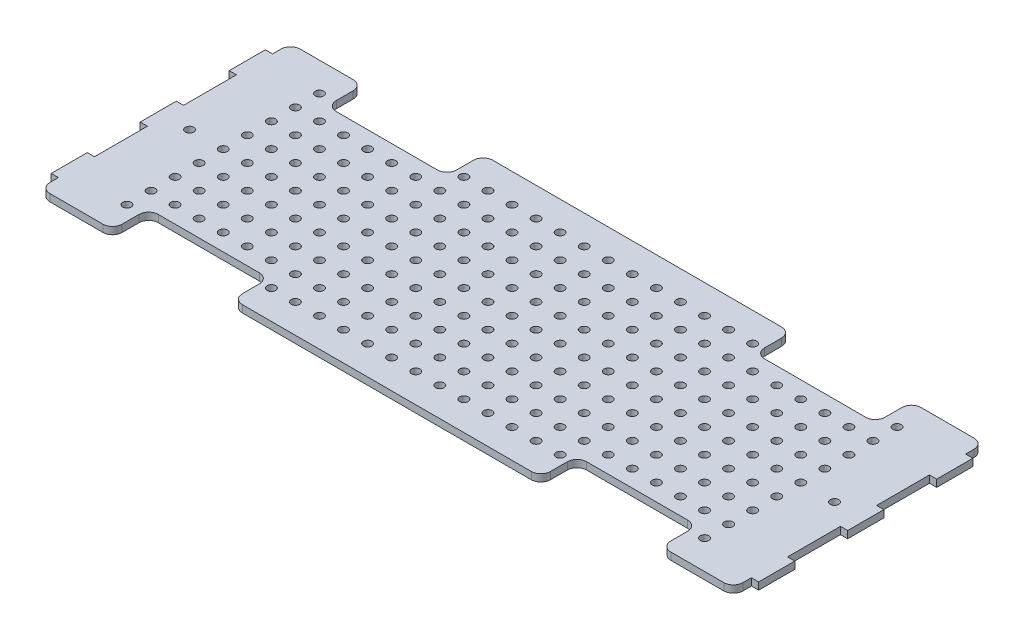
SolidWorks part; units mm, degrees
material "Акрил (Средняя-высокая ударопрочность)"
ref_plane "Спереди" through (0, 0, 0) normal (0, 0, 1) x (1, 0, 0)
ref_plane "Сверху" through (0, 0, 0) normal (0, 1, 0) x (1, 0, 0)
ref_plane "Справа" through (0, 0, 0) normal (1, 0, 0) x (0, 0, -1)
sketch "Эскиз1" plane through (0, 0, 0) normal (0, 1, 0) x (1, 0, 0)
  line L0 (0, 0) -> (87.657, 0) construction
  line L1 (-140, -52) -> (140, -52)
  line L2 (-144, -33.5845) -> (-144, -7.5)
  line L3 (-140, 52) -> (140, 52)
  line L4 (144, -48) -> (144, -37)
  line L5 (-144, -52) -> (144, 52) construction
  line L6 (-144, 52) -> (144, -52) construction
  line L7 (0, 0) -> (0, 35.739) construction
  line L8 (144, 37) -> (144, 48)
  line L9 (-144, 7.5) -> (-147, 7.5)
  line L10 (-147, 7.5) -> (-147, -7.5)
  line L11 (-147, -7.5) -> (-144, -7.5)
  line L12 (-144, 7.5) -> (-144, 18.5)
  line L13 (-144, 18.5) -> (-129.6514, 18.5)
  line L14 (-147, 44.5) -> (-144, 44.5)
  line L15 (-147, 29.5) -> (-147, 44.5)
  line L16 (-144, 29.5) -> (-147, 29.5)
  line L17 (-144, 37) -> (-144, 29.5)
  line L18 (-144, -37) -> (-144, -29.5)
  line L19 (-144, -29.5) -> (-147, -29.5)
  line L20 (-147, -29.5) -> (-147, -44.5)
  line L21 (-147, -44.5) -> (-144, -44.5)
  line L22 (147, -44.5) -> (144, -44.5)
  line L23 (147, -29.5) -> (147, -44.5)
  line L24 (144, -29.5) -> (147, -29.5)
  line L25 (-144, -44.5) -> (-144, -48)
  line L26 (144, 7.5) -> (144, 29.5)
  line L27 (144, 29.5) -> (147, 29.5)
  line L28 (147, 29.5) -> (147, 44.5)
  line L29 (147, 44.5) -> (144, 44.5)
  line L30 (144, 7.5) -> (144, 18.5)
  line L31 (147, -7.5) -> (144, -7.5)
  line L32 (147, 7.5) -> (147, -7.5)
  line L33 (144, 7.5) -> (147, 7.5)
  line L34 (144, -29.5) -> (144, 0)
  line L35 (-144, 52) -> (-118, 52)
  line L36 (-114, 48) -> (-114, 41)
  line L37 (-110, 37) -> (-68, 37)
  line L38 (-64, 41) -> (-64, 52)
  line L39 (-64, -41) -> (-64, -52)
  line L40 (-110, -37) -> (-68, -37)
  line L41 (-114, -52) -> (-114, -41)
  line L42 (114, -52) -> (114, -41)
  line L43 (110, -37) -> (68, -37)
  line L44 (64, -41) -> (64, -52)
  line L45 (64, 41) -> (64, 52)
  line L46 (110, 37) -> (68, 37)
  line L47 (114, 52) -> (114, 41)
  line L48 (0, 0) -> (120, 0)
  line L49 (-144, 44.5) -> (-144, 48)
  line L50 (-144, 7.5) -> (-144, 37)
  circle A0 centre (0, 0) radius 1.75
  circle A2 centre (120, 40) radius 1.75
  circle A3 centre (110, 40) radius 1.75
  circle A4 centre (100, 40) radius 1.75
  circle A5 centre (90, 40) radius 1.75
  circle A6 centre (80, 40) radius 1.75
  circle A7 centre (70, 40) radius 1.75
  circle A8 centre (60, 40) radius 1.75
  circle A9 centre (50, 40) radius 1.75
  circle A10 centre (40, 40) radius 1.75
  circle A11 centre (30, 40) radius 1.75
  circle A12 centre (20, 40) radius 1.75
  circle A13 centre (10, 40) radius 1.75
  circle A14 centre (0, 40) radius 1.75
  circle A15 centre (-10, 40) radius 1.75
  circle A16 centre (-20, 40) radius 1.75
  circle A17 centre (-30, 40) radius 1.75
  circle A18 centre (-40, 40) radius 1.75
  circle A19 centre (-50, 40) radius 1.75
  circle A20 centre (-60, 40) radius 1.75
  circle A21 centre (-70, 40) radius 1.75
  circle A22 centre (-80, 40) radius 1.75
  circle A23 centre (-90, 40) radius 1.75
  circle A24 centre (-100, 40) radius 1.75
  circle A25 centre (-110, 40) radius 1.75
  circle A26 centre (-120, 40) radius 1.75
  circle A27 centre (110, 30) radius 1.75
  circle A28 centre (100, 30) radius 1.75
  circle A29 centre (90, 30) radius 1.75
  circle A30 centre (80, 30) radius 1.75
  circle A31 centre (70, 30) radius 1.75
  circle A32 centre (60, 30) radius 1.75
  circle A33 centre (50, 30) radius 1.75
  circle A34 centre (40, 30) radius 1.75
  circle A35 centre (30, 30) radius 1.75
  circle A36 centre (20, 30) radius 1.75
  circle A37 centre (10, 30) radius 1.75
  circle A38 centre (0, 30) radius 1.75
  circle A39 centre (-10, 30) radius 1.75
  circle A40 centre (-20, 30) radius 1.75
  circle A41 centre (-30, 30) radius 1.75
  circle A42 centre (-40, 30) radius 1.75
  circle A43 centre (-50, 30) radius 1.75
  circle A44 centre (-60, 30) radius 1.75
  circle A45 centre (-70, 30) radius 1.75
  circle A46 centre (-80, 30) radius 1.75
  circle A47 centre (-90, 30) radius 1.75
  circle A48 centre (-100, 30) radius 1.75
  circle A49 centre (-110, 30) radius 1.75
  circle A50 centre (-120, 30) radius 1.75
  circle A51 centre (110, 20) radius 1.75
  circle A52 centre (100, 20) radius 1.75
  circle A53 centre (90, 20) radius 1.75
  circle A54 centre (80, 20) radius 1.75
  circle A55 centre (70, 20) radius 1.75
  circle A56 centre (60, 20) radius 1.75
  circle A57 centre (50, 20) radius 1.75
  circle A58 centre (40, 20) radius 1.75
  circle A59 centre (30, 20) radius 1.75
  circle A60 centre (20, 20) radius 1.75
  circle A61 centre (10, 20) radius 1.75
  circle A62 centre (0, 20) radius 1.75
  circle A63 centre (-10, 20) radius 1.75
  circle A64 centre (-20, 20) radius 1.75
  circle A65 centre (-30, 20) radius 1.75
  circle A66 centre (-40, 20) radius 1.75
  circle A67 centre (-50, 20) radius 1.75
  circle A68 centre (-60, 20) radius 1.75
  circle A69 centre (-70, 20) radius 1.75
  circle A70 centre (-80, 20) radius 1.75
  circle A71 centre (-90, 20) radius 1.75
  circle A72 centre (-100, 20) radius 1.75
  circle A73 centre (-110, 20) radius 1.75
  circle A74 centre (-120, 20) radius 1.75
  circle A75 centre (110, 10) radius 1.75
  circle A76 centre (100, 10) radius 1.75
  circle A77 centre (90, 10) radius 1.75
  circle A78 centre (80, 10) radius 1.75
  circle A79 centre (70, 10) radius 1.75
  circle A80 centre (60, 10) radius 1.75
  circle A81 centre (50, 10) radius 1.75
  circle A82 centre (40, 10) radius 1.75
  circle A83 centre (30, 10) radius 1.75
  circle A84 centre (20, 10) radius 1.75
  circle A85 centre (10, 10) radius 1.75
  circle A86 centre (0, 10) radius 1.75
  circle A87 centre (-10, 10) radius 1.75
  circle A88 centre (-20, 10) radius 1.75
  circle A89 centre (-30, 10) radius 1.75
  circle A90 centre (-40, 10) radius 1.75
  circle A91 centre (-50, 10) radius 1.75
  circle A92 centre (-60, 10) radius 1.75
  circle A93 centre (-70, 10) radius 1.75
  circle A94 centre (-80, 10) radius 1.75
  circle A95 centre (-90, 10) radius 1.75
  circle A96 centre (-100, 10) radius 1.75
  circle A97 centre (-110, 10) radius 1.75
  circle A98 centre (-120, 10) radius 1.75
  circle A99 centre (110, 0) radius 1.75
  circle A100 centre (100, 0) radius 1.75
  circle A101 centre (90, 0) radius 1.75
  circle A102 centre (80, 0) radius 1.75
  circle A103 centre (70, 0) radius 1.75
  circle A104 centre (60, 0) radius 1.75
  circle A105 centre (50, 0) radius 1.75
  circle A106 centre (40, 0) radius 1.75
  circle A107 centre (30, 0) radius 1.75
  circle A108 centre (20, 0) radius 1.75
  circle A109 centre (10, 0) radius 1.75
  circle A110 centre (0, 0) radius 1.75
  circle A111 centre (-10, 0) radius 1.75
  circle A112 centre (-20, 0) radius 1.75
  circle A113 centre (-30, 0) radius 1.75
  circle A114 centre (-40, 0) radius 1.75
  circle A115 centre (-50, 0) radius 1.75
  circle A116 centre (-60, 0) radius 1.75
  circle A117 centre (-70, 0) radius 1.75
  circle A118 centre (-80, 0) radius 1.75
  circle A119 centre (-90, 0) radius 1.75
  circle A120 centre (-100, 0) radius 1.75
  circle A121 centre (-110, 0) radius 1.75
  circle A122 centre (-120, 0) radius 1.75
  circle A123 centre (110, -10) radius 1.75
  circle A124 centre (100, -10) radius 1.75
  circle A125 centre (90, -10) radius 1.75
  circle A126 centre (80, -10) radius 1.75
  circle A127 centre (70, -10) radius 1.75
  circle A128 centre (60, -10) radius 1.75
  circle A129 centre (50, -10) radius 1.75
  circle A130 centre (40, -10) radius 1.75
  circle A131 centre (30, -10) radius 1.75
  circle A132 centre (20, -10) radius 1.75
  circle A133 centre (10, -10) radius 1.75
  circle A134 centre (0, -10) radius 1.75
  circle A135 centre (-10, -10) radius 1.75
  circle A136 centre (-20, -10) radius 1.75
  circle A137 centre (-30, -10) radius 1.75
  circle A138 centre (-40, -10) radius 1.75
  circle A139 centre (-50, -10) radius 1.75
  circle A140 centre (-60, -10) radius 1.75
  circle A141 centre (-70, -10) radius 1.75
  circle A142 centre (-80, -10) radius 1.75
  circle A143 centre (-90, -10) radius 1.75
  circle A144 centre (-100, -10) radius 1.75
  circle A145 centre (-110, -10) radius 1.75
  circle A146 centre (-120, -10) radius 1.75
  circle A147 centre (110, -20) radius 1.75
  circle A148 centre (100, -20) radius 1.75
  circle A149 centre (90, -20) radius 1.75
  circle A150 centre (80, -20) radius 1.75
  circle A151 centre (70, -20) radius 1.75
  circle A152 centre (60, -20) radius 1.75
  circle A153 centre (50, -20) radius 1.75
  circle A154 centre (40, -20) radius 1.75
  circle A155 centre (30, -20) radius 1.75
  circle A156 centre (20, -20) radius 1.75
  circle A157 centre (10, -20) radius 1.75
  circle A158 centre (0, -20) radius 1.75
  circle A159 centre (-10, -20) radius 1.75
  circle A160 centre (-20, -20) radius 1.75
  circle A161 centre (-30, -20) radius 1.75
  circle A162 centre (-40, -20) radius 1.75
  circle A163 centre (-50, -20) radius 1.75
  circle A164 centre (-60, -20) radius 1.75
  circle A165 centre (-70, -20) radius 1.75
  circle A166 centre (-80, -20) radius 1.75
  circle A167 centre (-90, -20) radius 1.75
  circle A168 centre (-100, -20) radius 1.75
  circle A169 centre (-110, -20) radius 1.75
  circle A170 centre (-120, -20) radius 1.75
  circle A171 centre (110, -30) radius 1.75
  circle A172 centre (100, -30) radius 1.75
  circle A173 centre (90, -30) radius 1.75
  circle A174 centre (80, -30) radius 1.75
  circle A175 centre (70, -30) radius 1.75
  circle A176 centre (60, -30) radius 1.75
  circle A177 centre (50, -30) radius 1.75
  circle A178 centre (40, -30) radius 1.75
  circle A179 centre (30, -30) radius 1.75
  circle A180 centre (20, -30) radius 1.75
  circle A181 centre (10, -30) radius 1.75
  circle A182 centre (0, -30) radius 1.75
  circle A183 centre (-10, -30) radius 1.75
  circle A184 centre (-20, -30) radius 1.75
  circle A185 centre (-30, -30) radius 1.75
  circle A186 centre (-40, -30) radius 1.75
  circle A187 centre (-50, -30) radius 1.75
  circle A188 centre (-60, -30) radius 1.75
  circle A189 centre (-70, -30) radius 1.75
  circle A190 centre (-80, -30) radius 1.75
  circle A191 centre (-90, -30) radius 1.75
  circle A192 centre (-100, -30) radius 1.75
  circle A193 centre (-110, -30) radius 1.75
  circle A194 centre (-120, -30) radius 1.75
  circle A195 centre (110, -40) radius 1.75
  circle A196 centre (100, -40) radius 1.75
  circle A197 centre (90, -40) radius 1.75
  circle A198 centre (80, -40) radius 1.75
  circle A199 centre (70, -40) radius 1.75
  circle A200 centre (60, -40) radius 1.75
  circle A201 centre (50, -40) radius 1.75
  circle A202 centre (40, -40) radius 1.75
  circle A203 centre (30, -40) radius 1.75
  circle A204 centre (20, -40) radius 1.75
  circle A205 centre (10, -40) radius 1.75
  circle A206 centre (0, -40) radius 1.75
  circle A207 centre (-10, -40) radius 1.75
  circle A208 centre (-20, -40) radius 1.75
  circle A209 centre (-30, -40) radius 1.75
  circle A210 centre (-40, -40) radius 1.75
  circle A211 centre (-50, -40) radius 1.75
  circle A212 centre (-60, -40) radius 1.75
  circle A213 centre (-70, -40) radius 1.75
  circle A214 centre (-80, -40) radius 1.75
  circle A215 centre (-90, -40) radius 1.75
  circle A216 centre (-100, -40) radius 1.75
  circle A217 centre (-110, -40) radius 1.75
  circle A218 centre (-120, -40) radius 1.75
  circle A219 centre (120, 30) radius 1.75
  circle A220 centre (120, 20) radius 1.75
  circle A221 centre (120, 10) radius 1.75
  circle A222 centre (120, 0) radius 1.75
  circle A223 centre (120, -10) radius 1.75
  circle A224 centre (120, -20) radius 1.75
  circle A225 centre (120, -30) radius 1.75
  circle A226 centre (120, -40) radius 1.75
  arc A227 (-140, -52) -> (-144, -48) centre (-140, -48) cw
  arc A228 (-110, -37) -> (-114, -41) centre (-110, -41) ccw
  arc A229 (-64, -41) -> (-68, -37) centre (-68, -41) ccw
  arc A230 (68, -37) -> (64, -41) centre (68, -41) ccw
  arc A231 (114, -41) -> (110, -37) centre (110, -41) ccw
  arc A232 (140, -52) -> (144, -48) centre (140, -48) ccw
  arc A233 (140, 52) -> (144, 48) centre (140, 48) cw
  arc A234 (110, 37) -> (114, 41) centre (110, 41) ccw
  arc A235 (64, 41) -> (68, 37) centre (68, 41) ccw
  arc A236 (-68, 37) -> (-64, 41) centre (-68, 41) ccw
  arc A237 (-114, 41) -> (-110, 37) centre (-110, 41) ccw
  arc A238 (-118, 52) -> (-114, 48) centre (-118, 48) cw
  arc A239 (-144, 48) -> (-140, 52) centre (-140, 48) cw
  circle A240 centre (-134, 0) radius 1.75
  circle A241 centre (134, 0) radius 1.75
  point P0 (0, 0)
  point P515 (-114, -37)
  point P518 (-64, -37)
  point P521 (64, -37)
  point P524 (114, -37)
  point P533 (114, 37)
  point P536 (64, 37)
  point P539 (-64, 37)
  point P542 (-114, 37)
  point P545 (-114, 52)
  dimension "D1" = 120
  dimension "D2" = 40
  dimension "D5" = 4
  dimension "D3" = 25
  dimension "D4" = 9
extrude "Бобышка-Вытянуть1" add sketch "Эскиз1" along normal blind 1.5 and the other way blind 1.5 contours A239 L49 L14 L15 L16 L50 L12 L9 L10 L11 L2 L19 L20 L21 L25 A227 L1 L41 A228 L40 A229 L39 L44 A230 L43 A231 L42 A232 L4 L22 L23 L24 L34 L31 L32 region at (-140.6233, 0, 48.6233)
fillet "Скругление1" radius 4 7 edges at (114, 0, -52) (64, 0, -52) (-64, 0, -52) (114, 0, 52) (64, 0, 52) (-64, 0, 52) (-114, 0, 52)
